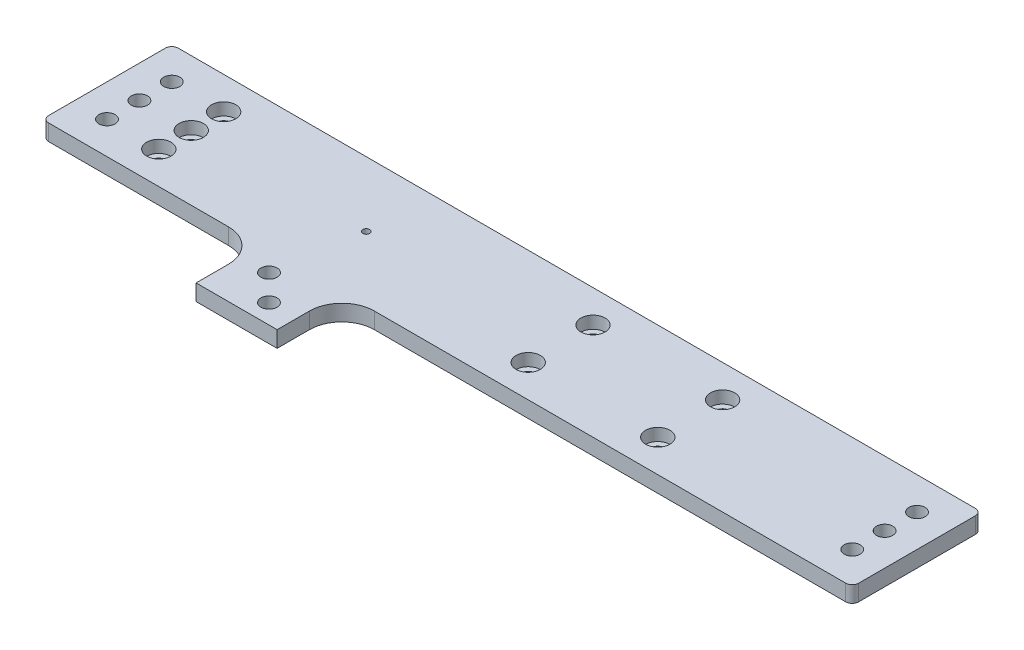
SolidWorks part; units mm, degrees
material "6061-T6 (SS)"
ref_plane "Front" through (0, 0, 0) normal (0, 0, 1) x (1, 0, 0)
ref_plane "Top" through (0, 0, 0) normal (0, 1, 0) x (1, 0, 0)
ref_plane "Right" through (0, 0, 0) normal (1, 0, 0) x (0, 0, -1)
sketch "Sketch1" plane through (0, 0, 0) normal (0, 1, 0) x (1, 0, 0)
  line L1 (-158.75, -25.4) -> (158.75, -25.4)
  line L2 (-158.75, -25.4) -> (-158.75, 25.4)
  line L3 (-158.75, 25.4) -> (158.75, 25.4)
  line L4 (158.75, -25.4) -> (158.75, 25.4)
  line L5 (-158.75, -25.4) -> (158.75, 25.4) construction
  line L6 (-158.75, 25.4) -> (158.75, -25.4) construction
  point P0 (0, 0)
  dimension "D1" = 50.8
  dimension "D2" = 317.5
extrude "Boss-Extrude1" add sketch "Sketch1" along normal blind 6.35
hole_wizard "CBORE for #10 Socket Head Cap Screw1" positions "Sketch2" profile "Sketch4" counterbore size "#10" standard "ANSI Inch" end condition through all
sketch "Sketch2" plane through (0, 6.35, 0) normal (0, 1, 0) x (1, 0, 0)
  line L2 (158.75, 25.4) -> (-158.75, 25.4) construction
  line L6 (-158.75, -25.4) -> (158.75, -25.4) construction
  line L8 (-158.75, 25.4) -> (-158.75, -25.4) construction
  line L12 (158.75, -25.4) -> (158.75, 25.4) construction
  line L15 (19.05, 12.7) -> (19.05, 25.4) construction
  line L17 (19.05, -12.7) -> (19.05, -25.4) construction
  line L18 (-125.73, -25.4) -> (-125.73, -12.7) construction
  line L20 (-125.73, 0) -> (-125.73, 12.7) construction
  line L21 (-125.73, 12.7) -> (-125.73, 25.4) construction
  line L22 (-125.73, 0) -> (-125.73, -12.7) construction
  point P64 (19.05, 12.7)
  point P66 (69.85, 12.7)
  point P68 (19.05, -12.7)
  point P70 (69.85, -12.7)
  point P92 (-125.73, 12.7)
  point P94 (-125.73, 0)
  point P102 (-125.73, -12.7)
  dimension "D2" = 50.8
  dimension "D3" = 25.4
  dimension "D4" = 88.9
  dimension "D5" = 33.02
sketch "Sketch4" plane through (-125.73, 6.35, 12.7) normal (1, 0, 0) x (0, 0, 1)
  line L0 (0, 0) -> (0, 6.35)
  line L1 (0, 6.35) -> (2.5527, 6.35)
  line L3 (2.5527, 6.35) -> (2.5527, 4.826)
  line L4 (2.5527, 4.826) -> (4.7625, 4.826)
  line L5 (4.7625, 4.826) -> (4.7625, 0)
  line L7 (4.7625, 0) -> (0, 0)
  line L11 (0, -6.35) -> (0, 107.95) construction
  dimension "Thru Hole Dia." = 5.1054
  dimension "Thru Hole Depth" = 6.35
  dimension "C'Bore Dia." = 9.525
  dimension "C'Bore Depth" = 4.826
sketch "Sketch7" plane through (0, 0, 0) normal (0, -1, 0) x (1, 0, 0)
  line L0 (-146.05, 25.4) -> (-146.05, 12.7) construction
  line L1 (-158.75, 25.4) -> (158.75, 25.4) construction
  line L2 (-146.05, 12.7) -> (-146.05, 0) construction
  line L3 (-146.05, 0) -> (-146.05, -12.7) construction
  line L4 (-146.05, -12.7) -> (-146.05, -25.4) construction
  line L5 (158.75, -25.4) -> (-158.75, -25.4) construction
  line L7 (-158.75, -25.4) -> (-158.75, 25.4) construction
  line L8 (146.05, 25.4) -> (146.05, 12.7) construction
  line L9 (146.05, 12.7) -> (146.05, 0) construction
  line L10 (146.05, 0) -> (146.05, -12.7) construction
  line L11 (146.05, -12.7) -> (146.05, -25.4) construction
  line L13 (158.75, 25.4) -> (158.75, -25.4) construction
  point P0 (-146.05, 12.7)
  point P2 (-146.05, 0)
  point P4 (-146.05, -12.7)
  point P6 (146.05, 12.7)
  point P8 (146.05, 0)
  point P10 (146.05, -12.7)
  dimension "D1" = 12.7
  dimension "D2" = 12.7
hole_wizard "1/4 (0.25) Diameter Hole1" positions "Sketch7" profile "Sketch6" hole size "1/4" standard "ANSI Inch" end condition through all
sketch "Sketch6" plane through (-146.05, 0, 12.7) normal (1, 0, 0) x (0, 0, -1)
  line L0 (0, 0) -> (0, 6.35)
  line L1 (0, 6.35) -> (3.175, 6.35)
  line L2 (3.175, 6.35) -> (3.175, 0)
  line L5 (3.175, 0) -> (0, 0)
  line L11 (0, -6.35) -> (0, 107.95) construction
  dimension "Thru Hole Dia." = 6.35
  dimension "Thru Hole Depth" = 6.35
sketch "Sketch10" plane through (0, 0, 0) normal (0, -1, 0) x (-1, 0, 0)
  line L0 (158.75, 25.4) -> (158.75, -25.4) construction
  point P0 (57.15, 0)
  dimension "D1" = 101.6
hole_wizard "#6-32 Tapped Hole1" positions "Sketch10" profile "Sketch9" tap size "#6-32" standard "ANSI Inch" end condition through all
sketch "Sketch9" plane through (-57.15, 0, 0) normal (1, 0, 0) x (0, 0, -1)
  line L0 (0, 0) -> (0, 6.35)
  line L1 (0, 6.35) -> (1.3525, 6.35)
  line L2 (1.3525, 6.35) -> (1.3525, 0)
  line L5 (1.3525, 0) -> (0, 0)
  line L11 (0, -6.35) -> (0, 107.95) construction
  dimension "Thru Tap Drill Dia." = 2.7051
  dimension "Thru Tap Drill Depth" = 6.35
cosmetic thread "Hole Thread1" parameters "D2"=3.5052
sketch "Sketch11" plane through (0, 0, 0) normal (0, -1, 0) x (1, 0, 0)
  line L0 (158.75, -25.4) -> (-158.75, -25.4) construction
  line L1 (-70.0118, -25.4) -> (-48.1024, -25.4)
  line L2 (-70.0118, -25.4) -> (-70.0118, -45.81)
  line L3 (-70.0118, -45.81) -> (-48.1024, -45.81)
  line L4 (-48.1024, -25.4) -> (-48.1024, -45.81)
extrude "Boss-Extrude2" [suppressed] add sketch "Sketch11" against normal up to surface (6.35 mm away) up to face at (-57.15, 6.35, -1.3526)
sketch "Sketch12" plane through (0, 6.35, 0) normal (0, 1, 0) x (1, 0, 0)
  line L0 (-158.75, -25.4) -> (158.75, -25.4) construction
  line L1 (-73.025, -25.4) -> (-41.275, -25.4)
  line L2 (-73.025, -25.4) -> (-73.025, -50.8)
  line L3 (-73.025, -50.8) -> (-41.275, -50.8)
  line L4 (-41.275, -25.4) -> (-41.275, -50.8)
  line L5 (-158.75, 25.4) -> (-158.75, -25.4) construction
  dimension "D1" = 85.725
  dimension "D2" = 31.75
  dimension "D3" = 25.4
extrude "Boss-Extrude3" add sketch "Sketch12" against normal up to surface (6.35 mm away) up to face at (-57.15, 0, -1.3526)
sketch "Sketch15" plane through (0, 0, 0) normal (0, -1, 0) x (-1, 0, 0)
  point P0 (52.07, -43.18)
  point P3 (62.23, -33.02)
hole_wizard "1/4 (0.25) Diameter Hole2" positions "Sketch15" profile "Sketch14" hole size "1/4" standard "ANSI Inch" end condition through all
sketch "Sketch14" plane through (-52.07, 0, 43.18) normal (1, 0, 0) x (0, 0, -1)
  line L0 (0, 0) -> (0, 6.35)
  line L1 (0, 6.35) -> (3.175, 6.35)
  line L2 (3.175, 6.35) -> (3.175, 0)
  line L5 (3.175, 0) -> (0, 0)
  line L11 (0, -6.35) -> (0, 107.95) construction
  dimension "Thru Hole Dia." = 6.35
  dimension "Thru Hole Depth" = 6.35
fillet "Fillet1" radius 12.7 2 edges at (-73.025, 3.175, 25.4) (-41.275, 3.175, 25.4)
fillet "Fillet2" radius 2.54 4 edges at (158.75, 3.175, 25.4) (158.75, 3.175, -25.4) (-158.75, 3.175, -25.4) (-158.75, 3.175, 25.4)
